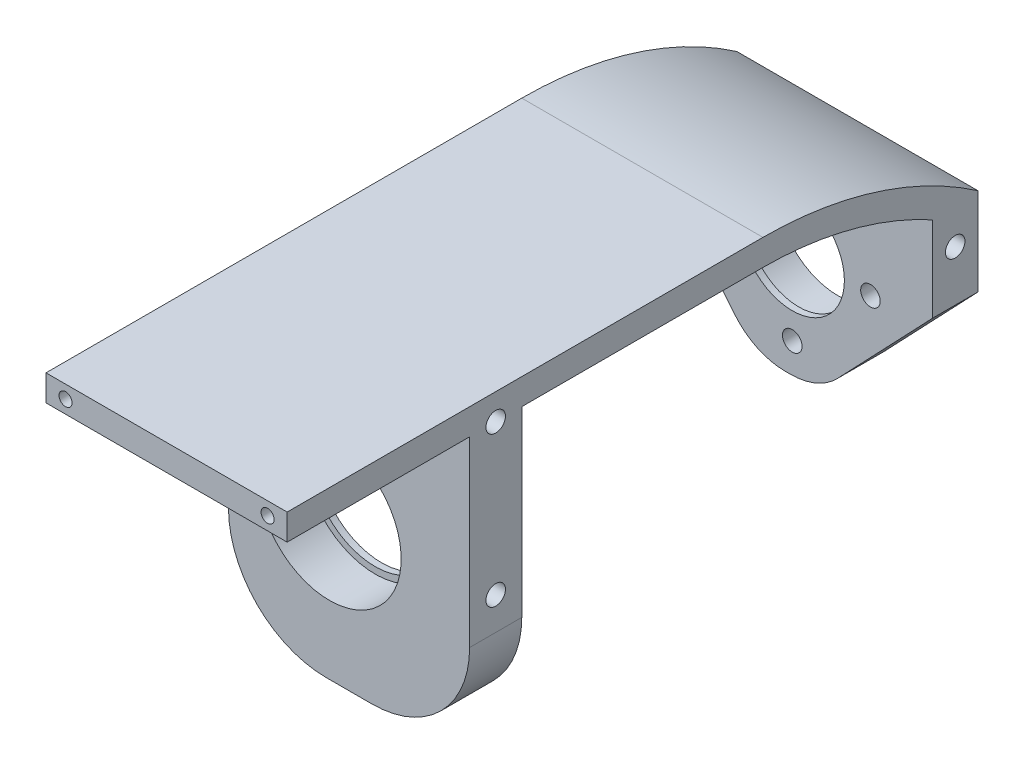
SolidWorks part; units mm, degrees
ref_plane "Front Plane" through (0, 0, 0) normal (0, 0, 1) x (1, 0, 0)
ref_plane "Top Plane" through (0, 0, 0) normal (0, 1, 0) x (1, 0, 0)
ref_plane "Right Plane" through (0, 0, 0) normal (1, 0, 0) x (0, 0, -1)
sketch "Sketch3" plane through (0, 0, 0) normal (1, 0, 0) x (0, 0, -1)
  line L0 (0, 0) -> (73, 0)
  line L1 (0, 0) -> (0, -4)
  line L2 (0, -4) -> (73, -4)
  line L4 (113.6909, -22.5) -> (70.143, -22.5) construction
  line L6 (90.9961, -30.5) -> (104.9961, -30.5) construction
  line L7 (90.9961, -30.5) -> (90.9961, -14.5) construction
  line L8 (90.9961, -14.5) -> (104.9961, -14.5) construction
  line L9 (104.9961, -30.5) -> (104.9961, -14.5) construction
  line L10 (90.9961, -30.5) -> (104.9961, -14.5) construction
  line L11 (90.9961, -14.5) -> (104.9961, -30.5) construction
  line L13 (109.8205, -18.5) -> (115.4706, -18.5)
  arc A0 (73, 0) -> (115.4706, -18.5) centre (73, -58) cw
  arc A1 (73, -4) -> (104.9961, -14.5) centre (73, -58) cw
  arc A2 (104.9961, -14.5) -> (109.8205, -18.5) centre (73, -58) cw
  point P9 (97.9961, -22.5)
  dimension "D1" = 58
  dimension "D2" = 4
  dimension "D3" = 73
  dimension "D4" = 22.5
  dimension "D5" = 16
  dimension "D6" = 4
  dimension "D7" = 14
extrude "Boss-Extrude1" add sketch "Sketch3" along normal blind 37
ref_plane "Plane1" through (21.5, 0, 0) normal (1, 0, 0) x (0, 0, -1)
sketch "Sketch4" plane through (37, 0, 0) normal (1, 0, 0) x (0, 0, -1)
  line L0 (28, -4) -> (28, -14.5)
  line L1 (0, -4) -> (73, -4) construction
  line L2 (114.75, -23.7518) -> (114.75, -33.7153) construction
  line L3 (0, 0) -> (0, -4) construction
  line L4 (28, -4) -> (36, -4)
  line L5 (36, -4) -> (36, -15.5)
  line L6 (36, -15.5) -> (35, -15.5) construction
  line L7 (35, -15.5) -> (35, -14.5) construction
  line L8 (35, -14.5) -> (28, -14.5) construction
  line L9 (35, -15.5) -> (35, -25.5) construction
  line L10 (35, -25.5) -> (17.1507, -25.5) construction
  line L11 (28, -14.5) -> (28, -36.5)
  line L12 (36, -15.5) -> (36, -35.5)
  line L13 (28, -47) -> (36, -47)
  line L14 (28, -47) -> (28, -36.5)
  line L15 (36, -47) -> (36, -35.5)
  line L16 (73, 0) -> (0, 0) construction
  arc A0 (109.8205, -18.5) -> (73, -4) centre (73, -58) ccw construction
  point P22 (28, -25.5)
  point P23 (36, -25.5)
  dimension "D1" = 28
  dimension "D2" = 114.75
  dimension "D3" = 25.5
  dimension "D4" = 8
  dimension "D5" = 7
  dimension "D6" = 11.5
  dimension "D7" = 11
extrude "Boss-Extrude3" add sketch "Sketch4" against normal up to surface (37 mm away) contours L11 L14 L13 L15 L12 L5 L4 L0 up to face at (0, -6.1802, -62.4324)
sketch "Sketch5" plane through (0, 0, -28) normal (0, 0, 1) x (1, 0, 0)
  line L0 (37, -25.5) -> (21.5, -25.5) construction
  line L1 (37, -47) -> (37, -4) construction
  circle A0 centre (21.5, -25.5) radius 11
  dimension "D2" = 22
  dimension "D1" = 15.5
  dimension "D3" = 21.5
extrude "Cut-Extrude1" cut sketch "Sketch5" against normal blind 7
sketch "Sketch6" plane through (0, 0, -35) normal (0, 0, 1) x (1, 0, 0)
  circle A0 centre (21.5, -25.5) radius 10
  dimension "D1" = 20
extrude "Cut-Extrude2" cut sketch "Sketch6" against normal blind 7
sketch "Sketch7" plane through (37, 0, 0) normal (1, 0, 0) x (0, 0, -1)
  line L0 (36, -4) -> (99, -4) construction
  line L1 (99, -4) -> (99, -10.6714) construction
  line L2 (67.5, -4) -> (67.5, -25.5) construction
  line L3 (67.5, -25.5) -> (116.1248, -25.5) construction
  line L4 (99, -10.6714) -> (99, -16) construction
  line L5 (99, -16) -> (105, -16) construction
  line L6 (105, -16) -> (105, -17.5) construction
  line L7 (105, -17.5) -> (106, -17.5) construction
  line L8 (106, -17.5) -> (106, -15.2566) construction
  line L9 (99, -10.6714) -> (99, -47)
  line L10 (99, -47) -> (106, -47)
  line L11 (106, -47) -> (106, -15.2566)
  arc A0 (109.8205, -18.5) -> (73, -4) centre (73, -58) ccw construction
  arc A2 (106, -15.2566) -> (99, -10.6714) centre (73, -58) ccw
  dimension "D1" = 63
  dimension "D2" = 21.5
  dimension "D3" = 9.5
  dimension "D4" = 8
  dimension "D5" = 6
  dimension "D6" = 1
  dimension "D7" = 43
extrude "Boss-Extrude4" add sketch "Sketch7" against normal up to surface (37 mm away) contours L11 A2 L9 L10 up to face at (0, -13.9081, -50.2594)
sketch "Sketch8" plane through (0, 0, -106) normal (0, 0, 1) x (1, 0, 0)
  circle A0 centre (21.5, -25.5) radius 9.5
  dimension "D1" = 19
extrude "Cut-Extrude3" cut sketch "Sketch8" along normal blind 6
sketch "Sketch9" plane through (0, 0, -100) normal (0, 0, -1) x (-1, 0, 0)
  circle A0 centre (-21.5, -25.5) radius 8
  dimension "D1" = 16
extrude "Cut-Extrude4" cut sketch "Sketch9" against normal blind 1
sketch "Sketch10" plane through (0, 0, -106) normal (0, 0, -1) x (-1, 0, 0)
  line L0 (0, -23.7577) -> (-17.4711, -42.0819)
  line L1 (0, -47) -> (0, -15.2566) construction
  line L2 (-17.4711, -42.0819) -> (-27.3185, -42.0819)
  line L3 (-27.3185, -42.0819) -> (-37, -30.2284)
  line L4 (-37, -47) -> (-37, -15.2566) construction
  line L5 (-37, -30.2284) -> (-37, -47)
  line L6 (-37, -47) -> (0, -47)
  line L7 (0, -47) -> (0, -23.7577)
extrude "Cut-Extrude5" cut sketch "Sketch10" against normal up to surface (7 mm away) up to face at (13.5, -25.5, -99)
sketch "Sketch11" plane through (37, 0, 0) normal (1, 0, 0) x (0, 0, -1)
  line L0 (106, -15.2566) -> (106, -10.303)
  line L1 (109.8205, -18.5) -> (115.4706, -18.5) construction
  line L2 (109.8205, -18.5) -> (115.4706, -18.5)
  arc A0 (115.4706, -18.5) -> (73, 0) centre (73, -58) ccw construction
  arc A1 (109.8205, -18.5) -> (106, -15.2566) centre (73, -58) ccw construction
  arc A2 (109.8205, -18.5) -> (106, -15.2566) centre (73, -58) ccw
  arc A3 (115.4706, -18.5) -> (106, -10.303) centre (73, -58) ccw
extrude "Cut-Extrude6" cut sketch "Sketch11" against normal through all
fillet "Fillet2" radius 10 2 edges at (17.4711, -42.0819, -102.5) (27.3185, -42.0819, -102.5)
sketch "Sketch12" plane through (0, 0, -99) normal (0, 0, 1) x (1, 0, 0)
  line L0 (21.5, -25.5) -> (21.5, -13.5) construction
  circle A0 centre (21.5, -13.5) radius 1.5
  circle A1 centre (33.5, -25.5) radius 1.5
  circle A2 centre (21.5, -37.5) radius 1.5
  circle A3 centre (9.5, -25.5) radius 1.5
  point P12 (21.5, -25.5)
  dimension "D1" = 3
  dimension "D3" = 12
  dimension "D4" = 12
  dimension "D5" = 12
  dimension "D2" = 4
extrude "Cut-Extrude7" cut sketch "Sketch12" against normal through all
sketch "Sketch13" [suppressed] plane through (0, 0, -28) normal (0, 0, 1) x (1, 0, 0)
  line L0 (23, 0) -> (23, -32) construction
  line L1 (37, 0) -> (0, 0) construction
  line L3 (0, -47) -> (0, -4) construction
  circle A0 centre (23, -32) radius 11
  dimension "D2" = 22
  dimension "D1" = 32
  dimension "D3" = 23
extrude "Cut-Extrude8" [suppressed] cut sketch "Sketch13" against normal blind 7 contours A0
sketch "Sketch14" [suppressed] plane through (0, 0, -35) normal (0, 0, 1) x (1, 0, 0)
  circle A0 centre (23, -32) radius 10
  dimension "D1" = 20
extrude "Cut-Extrude9" [suppressed] cut sketch "Sketch14" against normal blind 7
sketch "Sketch15" [suppressed] plane through (0, 0, 0) normal (-1, 0, 0) x (0, 0, 1)
  line L0 (-94, -8.2506) -> (-94, -47)
  line L1 (-94, -47) -> (-101, -47)
  line L2 (-101, -47) -> (-101, -11.8264)
  line L3 (-36, -4) -> (-36, -47) construction
  line L4 (-28, -47) -> (-36, -47) construction
  arc A0 (-73, -4) -> (-109.8205, -18.5) centre (-73, -58) ccw construction
  arc A1 (-94, -8.2506) -> (-101, -11.8264) centre (-73, -58) ccw
  dimension "D1" = 58
  dimension "D2" = 7
extrude "Boss-Extrude5" [suppressed] add sketch "Sketch15" against normal up to surface (37 mm away) up to face at (37, -15.6062, -57.1006)
sketch "Sketch16" [suppressed] plane through (0, 0, -94) normal (0, 0, 1) x (1, 0, 0)
  circle A0 centre (23, -32) radius 8
  dimension "D1" = 16
extrude "Cut-Extrude10" [suppressed] cut sketch "Sketch16" against normal blind 1
sketch "Sketch17" [suppressed] plane through (0, 0, -95) normal (0, 0, 1) x (1, 0, 0)
  circle A0 centre (23, -32) radius 9.5
  dimension "D1" = 19
extrude "Cut-Extrude11" [suppressed] cut sketch "Sketch17" against normal through all
sketch "Sketch18" [suppressed] plane through (37, 0, 0) normal (1, 0, 0) x (0, 0, -1)
  line L0 (101, -11.8264) -> (101, -7.2063)
  line L1 (109.8205, -18.5) -> (115.4706, -18.5) construction
  line L2 (109.8205, -18.5) -> (115.4706, -18.5)
  arc A0 (115.4706, -18.5) -> (73, 0) centre (73, -58) ccw construction
  arc A1 (109.8205, -18.5) -> (101, -11.8264) centre (73, -58) ccw construction
  arc A2 (115.4706, -18.5) -> (101, -7.2063) centre (73, -58) ccw
  arc A3 (109.8205, -18.5) -> (101, -11.8264) centre (73, -58) ccw
extrude "Cut-Extrude12" [suppressed] cut sketch "Sketch18" against normal through all
sketch "Sketch19" [suppressed] plane through (0, 0, -101) normal (0, 0, -1) x (-1, 0, 0)
  line L0 (-23, -32) -> (-23, -20) construction
  circle A0 centre (-23, -20) radius 1.5
  circle A1 centre (-11, -32) radius 1.5
  circle A2 centre (-23, -44) radius 1.5
  circle A3 centre (-35, -32) radius 1.5
  point P12 (-23, -32)
  dimension "D1" = 3
  dimension "D2" = 12
  dimension "D4" = 12
  dimension "D5" = 12
  dimension "D3" = 4
extrude "Cut-Extrude13" [suppressed] cut sketch "Sketch19" against normal up to surface (7 mm away)
fillet "Fillet3" [suppressed] radius 10
fillet "Fillet4" [suppressed] radius 10
fillet "Fillet5" radius 15 2 edges at (0, -47, -32) (37, -47, -32)
sketch "Sketch20" plane through (0, 0, 0) normal (-1, 0, 0) x (0, 0, 1)
  line L0 (-28, -4) -> (-36, -4) construction
  line L1 (-99, -10.6714) -> (-106, -10.6714) construction
  line L2 (-106, -23.7577) -> (-106, -10.303) construction
  line L3 (-102.5, -10.6714) -> (-102.5, -16) construction
  line L4 (-73, 0) -> (0, 0) construction
  line L5 (-32, -4) -> (-32, 0) construction
  line L6 (-32, -32) -> (-32, -27) construction
  line L7 (-36, -32) -> (-28, -32) construction
  line L8 (0, 0) -> (0, -4) construction
  circle A0 centre (-32, -4) radius 1.5
  circle A1 centre (-102.5, -16) radius 1.5
  circle A2 centre (-32, -27) radius 1.5
  dimension "D1" = 3
  dimension "D2" = 3
  dimension "D5" = 3
  dimension "D3" = 16
  dimension "D4" = 5
  dimension "D6" = 23
  dimension "D7" = 32
  dimension "D8" = 102.5
extrude "Cut-Extrude14" cut sketch "Sketch20" against normal blind 6
sketch "Sketch21" plane through (0, 0, 0) normal (0, 0, 1) x (1, 0, 0)
  line L0 (0, 0) -> (0, -4) construction
  line L1 (0, -2) -> (3, -2) construction
  line L2 (37, -2) -> (34, -2) construction
  line L3 (37, 0) -> (37, -4) construction
  circle A0 centre (3, -2) radius 1
  circle A1 centre (34, -2) radius 1
  dimension "D2" = 2
  dimension "D4" = 2
  dimension "D1" = 3
  dimension "D3" = 3
  dimension "D5" = 31
extrude "Cut-Extrude15" cut sketch "Sketch21" against normal blind 6 contours A0 | A1
sketch "Sketch22" [suppressed] plane through (0, 0, 0) normal (-1, 0, 0) x (0, 0, 1)
  line L0 (-94, -8.2506) -> (-101, -8.2506) construction
  line L1 (-101, -7.2063) -> (-101, -37) construction
  line L2 (-36, -4) -> (-28, -4) construction
  line L3 (-73, 0) -> (0, 0) construction
  circle A0 centre (-97.5, -16) radius 1.5
  circle A1 centre (-32, -4) radius 1.5
  circle A2 centre (-32, -27) radius 1.5
  point P7 (-97.5, -8.2506)
  dimension "D2" = 3
  dimension "D3" = 3
  dimension "D5" = 3
  dimension "D1" = 16
  dimension "D4" = 23
extrude "Cut-Extrude16" [suppressed] cut sketch "Sketch22" against normal blind 6
mirror "Mirror1" about plane through (37, -58, -73) normal (-1, 0, 0) of bodies 121
delete or keep bodies "Body-Delete/Keep 1" type delete bodies bodies 121
mirror "Mirror2" [suppressed] of bodies 122
delete or keep bodies "Body-Delete/Keep 2" [suppressed] type delete bodies bodies 122
equation "\"mini-flipper-shaft-diameter\"= 26mm"
equation "\"mini-shaft-ring-groove-diam\"= 7.8mm"
equation "\"mini-shaft-ring-groove-width\"= 1mm"
equation "\"dtCoverPlate-DistFrom-GearCent\"= 73mm"
equation "\"wormGearShaft-L\"= \"dtCoverPlate-DistFrom-GearCent\" - 27.75 + 3.75"
equation "\"wormGearShaft-Dsmall\"= 6mm"
equation "\"wormGearShaft-Dworm\"= 12mm"
equation "\"wormL-D\"= 12mm"
equation "\"wormR-D\"= 15mm"
equation "\"wormGearL-D\"= 40mm"
equation "\"wormGearR-D\"= 50mm"
